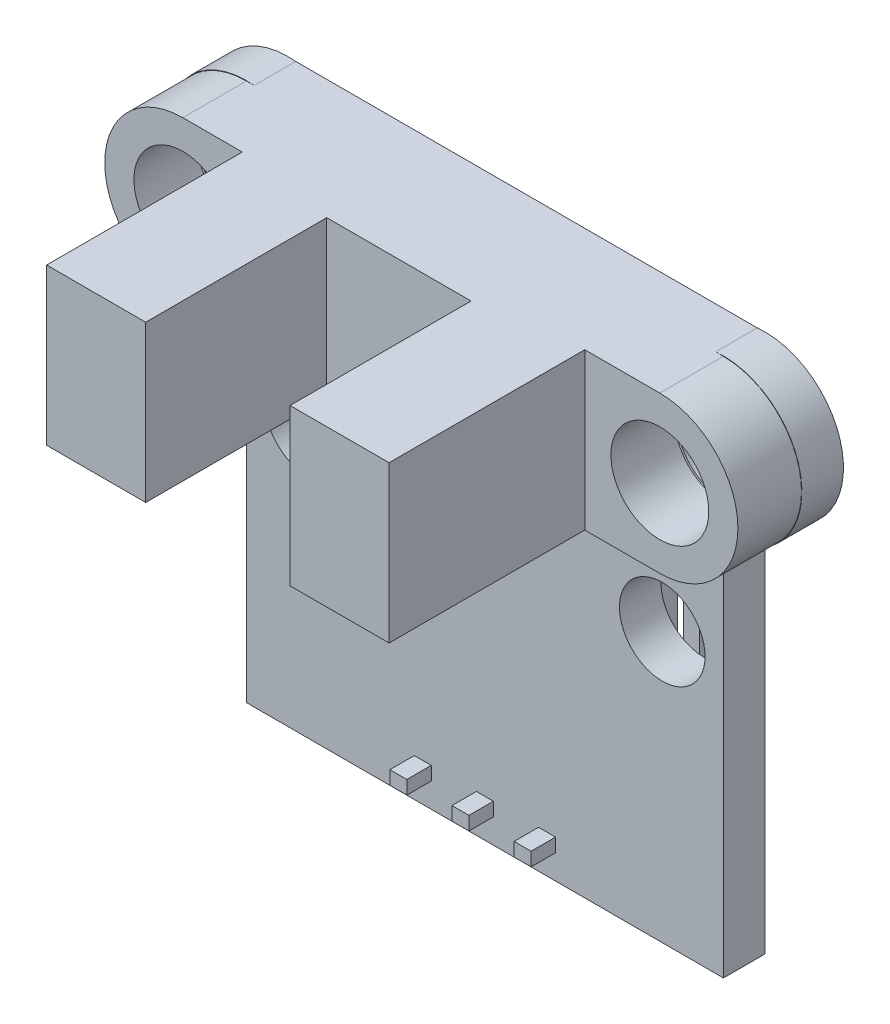
SolidWorks part; units mm, degrees
ref_plane "Ön Düzlem" through (0, 0, 0) normal (0, 0, 1) x (1, 0, 0)
ref_plane "Üst Düzlem" through (0, 0, 0) normal (0, 1, 0) x (1, 0, 0)
ref_plane "Sağ Düzlem" through (0, 0, 0) normal (1, 0, 0) x (0, 0, -1)
sketch "Çizim1" plane through (0, 0, 0) normal (0, 0, 1) x (1, 0, 0)
  line L0 (10.068, -11) -> (7.568, -11) construction
  line L1 (-9.432, -11) -> (10.068, -11)
  line L2 (-9.432, -11) -> (-9.432, 4.6)
  line L3 (-9.1139, 11) -> (9.75, 11)
  line L4 (10.068, -11) -> (10.068, 4.6)
  line L5 (7.568, -11) -> (7.568, 0) construction
  line L9 (0.318, 11) -> (0.318, -11) construction
  arc A0 (10.068, 4.6) -> (9.75, 11) centre (10.068, 7.8079) ccw
  circle A1 centre (10.068, 7.8079) radius 1.9006
  circle A2 centre (-9.432, 7.8079) radius 1.9006
  arc A3 (-9.432, 4.6) -> (-9.1139, 11) centre (-9.432, 7.8079) cw
  circle A4 centre (7.568, 0) radius 1.75
  circle A5 centre (-6.932, 0) radius 1.75
  point P0 (0, 0)
  dimension "D1" = 22
  dimension "D3" = 3.5
  dimension "D2" = 11
  dimension "D4" = 19.5
  dimension "D5" = 2.5
  dimension "D6" = 6.4
extrude "Yükseklik-Ekstrüzyon1" add sketch "Çizim1" along normal blind 1.7
sketch "Çizim2" plane through (0, 0, 1.7) normal (0, 0, 1) x (1, 0, 0)
  line L0 (-9.432, 11) -> (10.068, 11)
  line L1 (10.068, 4.6158) -> (-9.432, 4.6158)
  line L2 (9.75, 11) -> (-9.1139, 11) construction
  arc A0 (10.068, 4.6158) -> (10.068, 11) centre (10.068, 7.8079) ccw
  arc A1 (-9.432, 11) -> (-9.432, 4.6158) centre (-9.432, 7.8079) ccw
  circle A2 centre (-9.432, 7.8079) radius 2
  circle A3 centre (10.068, 7.8079) radius 2
extrude "Yükseklik-Ekstrüzyon2" add sketch "Çizim2" along normal blind 2.6
sketch "Çizim3" plane through (0, 0, 4.3) normal (0, 0, 1) x (1, 0, 0)
  line L0 (10.068, 11) -> (-9.432, 11) construction
  line L1 (0, 7.925) -> (0, 4.9813) construction
  line L2 (-9.432, 4.6158) -> (10.068, 4.6158) construction
  line L3 (2.95, 4.6158) -> (7.0001, 4.6158)
  line L4 (-7.0001, 11) -> (-2.95, 11)
  line L5 (-7.0001, 11) -> (-7.0001, 4.6158)
  line L6 (-7.0001, 4.6158) -> (-2.95, 4.6158)
  line L7 (7.0001, 11) -> (7.0001, 4.6158)
  line L11 (-2.95, 11) -> (-2.95, 4.6158)
  line L13 (2.95, 11) -> (2.95, 4.6158)
  line L18 (2.95, 11) -> (7.0001, 11)
  point P6 (0, 7.925)
  point P11 (0, 7.925)
  dimension "D1" = 5.9
extrude "Yükseklik-Ekstrüzyon3" add sketch "Çizim3" along normal blind 8
sketch "Çizim4" plane through (0, 0, 4.3) normal (0, 0, 1) x (1, 0, 0)
  line L4 (2.95, 11) -> (-2.95, 11)
  line L5 (-2.95, 11) -> (-2.95, 4.6158)
  line L6 (-2.95, 4.6158) -> (2.95, 4.6158)
  line L7 (2.95, 4.6158) -> (2.95, 11)
  line L8 (2.95, 11) -> (-2.95, 11)
  line L9 (-2.95, 11) -> (-2.95, 4.6158)
  line L10 (-2.95, 4.6158) -> (2.95, 4.6158)
  line L11 (2.95, 4.6158) -> (2.95, 11)
  dimension "D1" = 0
extrude "Yükseklik-Ekstrüzyon4" add sketch "Çizim4" along normal blind 0.6
sketch "Çizim5" plane through (0, 0, 0) normal (0, 0, -1) x (-1, 0, 0)
  line L0 (9.432, -11) -> (-10.068, -11) construction
  line L5 (-0.318, -11) -> (-0.318, -8.46) construction
  line L6 (0.702, -8.46) -> (0.952, -8.71)
  line L8 (-1.338, -8.46) -> (0.702, -8.46)
  line L9 (-1.588, -8.71) -> (-1.588, -10.75)
  line L10 (-1.338, -11) -> (0.702, -11)
  line L11 (0.952, -8.71) -> (0.952, -10.75)
  line L12 (-1.588, -8.46) -> (0.952, -11) construction
  line L13 (-1.588, -11) -> (0.952, -8.46) construction
  line L14 (0.702, -11) -> (0.952, -10.75)
  line L15 (-1.588, -10.75) -> (-1.338, -11)
  line L16 (-1.588, -8.71) -> (-1.338, -8.46)
  line L17 (-1.838, -11) -> (-3.878, -11)
  line L18 (-3.878, -11) -> (-4.128, -10.75)
  line L19 (-4.128, -8.71) -> (-4.128, -10.75)
  line L20 (-3.878, -8.46) -> (-4.128, -8.71)
  line L21 (-1.838, -8.46) -> (-3.878, -8.46)
  line L22 (-1.588, -10.75) -> (-1.838, -11)
  line L23 (-1.588, -8.71) -> (-1.838, -8.46)
  line L24 (3.242, -11) -> (1.202, -11)
  line L25 (1.202, -11) -> (0.952, -10.75)
  line L26 (1.202, -8.46) -> (0.952, -8.71)
  line L27 (3.242, -8.46) -> (1.202, -8.46)
  line L28 (3.492, -10.75) -> (3.242, -11)
  line L29 (3.492, -8.71) -> (3.242, -8.46)
  line L30 (3.492, -8.71) -> (3.492, -10.75)
  point P0 (-0.318, -11)
  point P3 (-0.318, -9.73)
  line M15 (-10.068, -11) -> (9.432, -11)
extrude "Yükseklik-Ekstrüzyon6" add sketch "Çizim5" along normal blind 2.54 contours L9 L23 L21 L20 L19 L18 L22 M15 | L16 L9 L15 L14 L11 L6 L8 M15 | L30 L29 L27 L26 L11 L25 L28 M15 region at (0.318, -9.73, 0) region at (-2.222, -9.73, 0) region at (2.858, -9.73, 0)
sketch "Çizim6" plane through (0, -11, 0) normal (0, -1, 0) x (1, 0, 0)
  line L1 (-9.432, 1.7) -> (10.068, 1.7)
  line L2 (-9.432, 1.7) -> (-9.432, 0)
  line L3 (-9.432, 0) -> (10.068, 0)
  line L4 (10.068, 1.7) -> (10.068, 0)
extrude "Yükseklik-Ekstrüzyon7" add sketch "Çizim6" along normal blind 0.01
sketch "Çizim7" plane through (2.95, 0, 0) normal (-1, 0, 0) x (0, 0, 1)
  line L0 (4.9, 7.8079) -> (11.65, 7.8079) construction
  line L1 (4.9, 4.6158) -> (4.9, 11) construction
  line L3 (4.9, 8.1829) -> (11.65, 8.1829)
  line L4 (4.9, 8.1829) -> (4.9, 7.4329)
  line L5 (4.9, 7.4329) -> (11.65, 7.4329)
  line L6 (11.65, 8.1829) -> (11.65, 7.4329)
  line L7 (4.9, 8.1829) -> (11.65, 7.4329) construction
  line L8 (4.9, 7.4329) -> (11.65, 8.1829) construction
  point P4 (8.275, 7.8079)
extrude "Kes-Ekstrüzyon1" cut sketch "Çizim7" against normal blind 0.1 and the other way blind 5.9
sketch "Çizim8" plane through (0, 0, -2.54) normal (0, 0, -1) x (-1, 0, 0)
  line L0 (-1.588, -8.71) -> (-1.588, -10.75) construction
  line L3 (0.952, -8.71) -> (0.952, -10.75) construction
  line L4 (0.827, -10.875) -> (-1.463, -8.585) construction
  line L5 (0.702, -11) -> (0.952, -10.75) construction
  line L6 (-1.588, -8.71) -> (-1.338, -8.46) construction
  line L7 (2.5544, -9.3975) -> (1.8895, -9.3975)
  line L8 (-0.6505, -10.0625) -> (0.0144, -10.0625)
  line L9 (-0.6505, -10.0625) -> (-0.6505, -9.3975)
  line L10 (-0.6505, -9.3975) -> (0.0144, -9.3975)
  line L11 (0.0144, -10.0625) -> (0.0144, -9.3975)
  line L12 (-0.6505, -10.0625) -> (0.0144, -9.3975) construction
  line L13 (-0.6505, -9.3975) -> (0.0144, -10.0625) construction
  line L14 (1.8895, -10.0625) -> (1.8895, -9.3975)
  line L15 (2.5544, -10.0625) -> (1.8895, -10.0625)
  line L16 (2.5544, -10.0625) -> (2.5544, -9.3975)
  line L17 (-2.5256, -9.3975) -> (-3.1905, -9.3975)
  line L18 (-3.1905, -10.0625) -> (-3.1905, -9.3975)
  line L19 (-2.5256, -10.0625) -> (-3.1905, -10.0625)
  line L20 (-2.5256, -10.0625) -> (-2.5256, -9.3975)
  point P14 (-0.318, -9.73)
ref_plane "Düzlem1" through (0, 0, 0) normal (1, 0, 0) x (0, 0, -1)
sketch "Çizim9" plane through (0, 0, 0) normal (1, 0, 0) x (0, 0, -1)
  line L0 (2.54, -9.73) -> (4.04, -9.73)
  line L1 (4.54, -9.23) -> (4.54, -3.305)
  arc A0 (4.04, -9.73) -> (4.54, -9.23) centre (4.04, -9.23) ccw
  dimension "D1" = 0.5
sweep "Süpür1" add profiles "Çizim8" path "Çizim9"
sketch "Çizim10" plane through (0, 0, -2.54) normal (0, 0, -1) x (-1, 0, 0)
  line L20 (-1.838, -11) -> (-1.588, -10.75)
  line L21 (-1.588, -10.75) -> (-1.338, -11)
  line L22 (-1.338, -11) -> (0.702, -11)
  line L23 (0.702, -11) -> (0.952, -10.75)
  line L24 (0.952, -10.75) -> (1.202, -11)
  line L25 (1.202, -11) -> (3.242, -11)
  line L26 (3.242, -11) -> (3.492, -10.75)
  line L27 (3.492, -10.75) -> (3.492, -8.71)
  line L28 (3.492, -8.71) -> (3.242, -8.46)
  line L29 (3.242, -8.46) -> (1.202, -8.46)
  line L30 (1.202, -8.46) -> (0.952, -8.71)
  line L31 (0.952, -8.71) -> (0.702, -8.46)
  line L32 (0.702, -8.46) -> (-1.338, -8.46)
  line L33 (-1.338, -8.46) -> (-1.588, -8.71)
  line L34 (-1.588, -8.71) -> (-1.838, -8.46)
  line L35 (-1.838, -8.46) -> (-3.878, -8.46)
  line L36 (-3.878, -8.46) -> (-4.128, -8.71)
  line L37 (-4.128, -8.71) -> (-4.128, -10.75)
  line L38 (-4.128, -10.75) -> (-3.878, -11)
  line L39 (-3.878, -11) -> (-1.838, -11)
  line L40 (-1.838, -11) -> (-1.588, -10.75)
  line L41 (-1.588, -10.75) -> (-1.338, -11)
  line L42 (-1.338, -11) -> (0.702, -11)
  line L43 (0.702, -11) -> (0.952, -10.75)
  line L44 (0.952, -10.75) -> (1.202, -11)
  line L45 (1.202, -11) -> (3.242, -11)
  line L46 (3.242, -11) -> (3.492, -10.75)
  line L47 (3.492, -10.75) -> (3.492, -8.71)
  line L48 (3.492, -8.71) -> (3.242, -8.46)
  line L49 (3.242, -8.46) -> (1.202, -8.46)
  line L50 (1.202, -8.46) -> (0.952, -8.71)
  line L51 (0.952, -8.71) -> (0.702, -8.46)
  line L52 (0.702, -8.46) -> (-1.338, -8.46)
  line L53 (-1.338, -8.46) -> (-1.588, -8.71)
  line L54 (-1.588, -8.71) -> (-1.838, -8.46)
  line L55 (-1.838, -8.46) -> (-3.878, -8.46)
  line L56 (-3.878, -8.46) -> (-4.128, -8.71)
  line L57 (-4.128, -8.71) -> (-4.128, -10.75)
  line L58 (-4.128, -10.75) -> (-3.878, -11)
  line L59 (-3.878, -11) -> (-1.838, -11)
  dimension "D1" = 0
sketch "Çizim11" plane through (0, 0, 1.7) normal (0, 0, 1) x (1, 0, 0)
  line L0 (-0.952, -8.71) -> (-0.952, -10.75) construction
  line L1 (0.318, -8.46) -> (0.318, -11) construction
  line L2 (-0.702, -8.46) -> (1.338, -8.46) construction
  line L3 (1.338, -11) -> (-0.702, -11) construction
  line L4 (1.588, -8.71) -> (1.588, -10.75) construction
  line L5 (-1.8754, -10.0071) -> (-2.5686, -10.0071)
  line L6 (-0.0286, -9.4529) -> (0.6646, -9.4529)
  line L7 (-0.0286, -9.4529) -> (-0.0286, -10.0071)
  line L8 (-0.0286, -10.0071) -> (0.6646, -10.0071)
  line L9 (0.6646, -9.4529) -> (0.6646, -10.0071)
  line L10 (-0.0286, -9.4529) -> (0.6646, -10.0071) construction
  line L11 (-0.0286, -10.0071) -> (0.6646, -9.4529) construction
  line L12 (-2.5686, -9.4529) -> (-2.5686, -10.0071)
  line L13 (-1.8754, -9.4529) -> (-2.5686, -9.4529)
  line L14 (-1.8754, -9.4529) -> (-1.8754, -10.0071)
  line L15 (3.2046, -10.0071) -> (2.5114, -10.0071)
  line L16 (2.5114, -9.4529) -> (2.5114, -10.0071)
  line L17 (3.2046, -9.4529) -> (2.5114, -9.4529)
  line L18 (3.2046, -9.4529) -> (3.2046, -10.0071)
  point P14 (0.318, -9.73)
extrude "Yükseklik-Ekstrüzyon8" add sketch "Çizim11" along normal blind 1
sketch "Çizim12" plane through (0, 0, 0) normal (0, 0, -1) x (-1, 0, 0)
  line L0 (-10.068, 0) -> (-4.9982, 0) construction
  line L1 (-10.068, -11.01) -> (-10.068, 4.6) construction
  line L2 (-4.9982, 0) -> (-4.9982, 2.3312)
  line L3 (-4.9982, 2.3312) -> (-1.2034, 2.3312)
  line L4 (-1.2034, 2.3312) -> (-1.2034, -3.046)
  line L5 (-1.2034, -3.046) -> (-4.9982, -3.046)
  line L6 (-4.9982, -3.046) -> (-4.9982, 0)
extrude "Yükseklik-Ekstrüzyon9" add sketch "Çizim12" along normal blind 1.5
